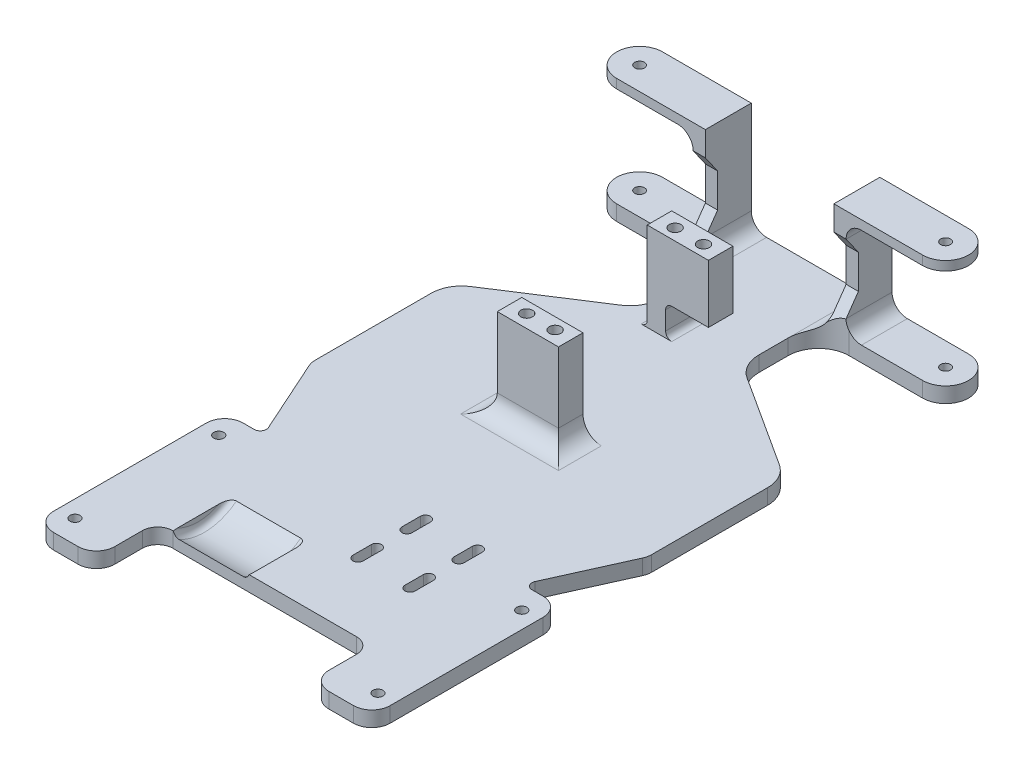
SolidWorks part; units mm, degrees
ref_plane "Front Plane" through (0, 0, 0) normal (0, 0, 1) x (1, 0, 0)
ref_plane "Top Plane" through (0, 0, 0) normal (0, 1, 0) x (1, 0, 0)
ref_plane "Right Plane" through (0, 0, 0) normal (1, 0, 0) x (0, 0, -1)
sketch "Sketch1" plane through (0, 0, 0) normal (0, 1, 0) x (1, 0, 0)
  line L1 (0, 0) -> (100, 0)
  line L2 (0, 0) -> (0, 15)
  line L3 (0, 15) -> (100, 15)
  line L4 (100, 0) -> (100, 15)
  circle A0 centre (100, 7.5) radius 7.5
  circle A1 centre (0, 7.5) radius 7.5
  circle A2 centre (0, 7.5) radius 1.6
  circle A3 centre (100, 7.5) radius 1.6
  dimension "D3" = 3.2
  dimension "D1" = 100
  dimension "D2" = 15
extrude "Boss-Extrude3" add sketch "Sketch1" along normal blind 5 contours A2 L2 A1 | A2 L2 A1 | A1 L1 A0 L3 | A3 L4 A0 | A3 L4 A0 region at (50, 0, -7.5) region at (-3.3025, 0, -7.5) region at (3.3025, 0, -7.5) region at (96.6975, 0, -7.5) region at (103.3025, 0, -7.5)
sketch "Sketch2" plane through (0, 5, 0) normal (0, 1, 0) x (1, 0, 0)
  line L0 (0, 15) -> (100, 15) construction
  line L1 (25, 15) -> (29, 15)
  line L2 (25, 15) -> (25, 0)
  line L3 (25, 0) -> (29, 0)
  line L4 (29, 15) -> (29, 0)
  line L5 (0, 0) -> (100, 0) construction
  line L6 (50, 0) -> (50, 15) construction
  line L7 (75, 0) -> (71, 0)
  line L8 (71, 15) -> (71, 0)
  line L9 (75, 15) -> (71, 15)
  line L10 (75, 15) -> (75, 0)
  circle A0 centre (0, 7.5) radius 1.6 construction
  dimension "D2" = 25
  dimension "D1" = 4
extrude "Boss-Extrude4" add sketch "Sketch2" along normal blind 32.5
sketch "Sketch3" plane through (0, 37.5, 0) normal (0, 1, 0) x (1, 0, 0)
  line L0 (75, 0) -> (75, 15) construction
  line L1 (75, 15) -> (71, 15) construction
  line L2 (71, 15) -> (71, 0) construction
  line L3 (71, 0) -> (75, 0) construction
  line L4 (25, 15) -> (25, 0) construction
  line L5 (25, 0) -> (29, 0) construction
  line L6 (29, 0) -> (29, 15) construction
  line L7 (29, 15) -> (25, 15) construction
  line L8 (25, 0) -> (25, 15) construction
  line L9 (25, 15) -> (0, 15) construction
  line L10 (0, 0) -> (25, 0) construction
  line L11 (100, 15) -> (75, 15) construction
  line L12 (75, 15) -> (75, 0) construction
  line L13 (75, 0) -> (100, 0) construction
  line L18 (75, 0) -> (75, 15)
  line L19 (75, 15) -> (71, 15)
  line L20 (71, 15) -> (71, 0)
  line L21 (71, 0) -> (75, 0)
  line L22 (25, 15) -> (25, 0)
  line L23 (25, 0) -> (29, 0)
  line L24 (29, 0) -> (29, 15)
  line L25 (29, 15) -> (25, 15)
  line L26 (25, 0) -> (25, 15)
  line L27 (25, 15) -> (0, 15)
  line L28 (0, 0) -> (25, 0)
  line L29 (100, 15) -> (75, 15)
  line L30 (75, 15) -> (75, 0)
  line L31 (75, 0) -> (100, 0)
  arc A0 (0, 15) -> (0, 0) centre (0, 7.5) ccw construction
  arc A1 (100, 0) -> (100, 15) centre (100, 7.5) ccw construction
  arc A2 (0, 15) -> (0, 0) centre (0, 7.5) ccw
  arc A3 (100, 0) -> (100, 15) centre (100, 7.5) ccw
  circle A4 centre (0, 7.5) radius 1.6
  circle A5 centre (100, 7.5) radius 1.6
  line M18 (25, 15) -> (25, 0)
  line M19 (25, 0) -> (29, 0)
  line M20 (29, 0) -> (29, 15)
  line M21 (29, 15) -> (25, 15)
  dimension "D1" = 3.2
extrude "Boss-Extrude6" add sketch "Sketch3" along normal blind 3 contours L31 A3 L29 L18 A5 | L20 L21 L18 L19 | L27 A2 L28 A4 M18 | M21 M18 M19 M20 region at (73, 37.5, -7.5) region at (90.3226, 37.5, -7.5) region at (27, 37.5, -7.5) region at (9.6774, 37.5, -7.5)
fillet "Fillet1" radius 5 6 edges at (75, 5, -7.5) (25, 5, -7.5) (75, 37.5, -7.5) (25, 37.5, -7.5) (71, 5, -7.5) (29, 5, -7.5)
sketch "Sketch4" plane through (29, 0, 0) normal (1, 0, 0) x (0, 0, -1)
  line L0 (0, 32.5) -> (0, 10) construction
  line L1 (0, 32.5) -> (4, 32.5) construction
  line L2 (0, 32.5) -> (0, 10)
  line L3 (0, 10) -> (4, 10)
  line L4 (4, 26.7874) -> (4, 15.7126)
  line L5 (0, 10) -> (15, 10) construction
  line L6 (15, 32.5) -> (0, 32.5) construction
  line L7 (0, 32.5) -> (4, 26.7874)
  line L8 (0, 10) -> (4, 15.7126)
  dimension "D1" = 4
  dimension "D2" = 55
  dimension "D3" = 4
  dimension "D4" = 4
extrude "Cut-Extrude1" cut sketch "Sketch4" against normal blind 10 and the other way through all contours L8 L4 L7 L2
sketch "Sketch5" plane through (0, 0, 0) normal (0, -1, 0) x (1, 0, 0)
  line L0 (0, -15) -> (100, -15) construction
  line L1 (40, -15) -> (60, -15)
  line L2 (40, -15) -> (40, 80)
  line L3 (40, 80) -> (60, 80)
  line L4 (60, -15) -> (60, 80)
  point P6 (50, -15)
  point P7 (50, -15)
  dimension "D1" = 20
  dimension "D2" = 95
extrude "Boss-Extrude7" add sketch "Sketch5" against normal blind 5
sketch "Sketch6" plane through (0, 5, 0) normal (0, 1, 0) x (1, 0, 0)
  line L0 (40, -80) -> (40, 0) construction
  line L1 (40, -30) -> (60, -30) construction
  line L2 (40, -30) -> (40, -71) construction
  line L3 (40, -71) -> (60, -71) construction
  line L4 (60, -30) -> (60, -71) construction
  line L5 (60, 0) -> (60, -80) construction
  line L6 (60, 0) -> (66, 0) construction
  line L7 (40, -22) -> (60, -22)
  line L8 (40, -71) -> (60, -71)
  line L9 (40, -71) -> (40, -79)
  line L10 (40, -79) -> (60, -79)
  line L11 (60, -71) -> (60, -79)
  line L12 (40, -22) -> (40, -30)
  line L13 (40, -30) -> (60, -30)
  line L14 (60, -22) -> (60, -30)
  dimension "D1" = 41
  dimension "D2" = 30
  dimension "D3" = 8
  dimension "D4" = 8
extrude "Boss-Extrude8" add sketch "Sketch6" along normal blind 29
sketch "Sketch7" plane through (0, 34, 0) normal (0, 1, 0) x (1, 0, 0)
  line L1 (50, -71) -> (50, -69.0543) construction
  line L2 (60, -71) -> (40, -71) construction
  line L3 (60, -50.5) -> (71.2332, -50.5) construction
  line L4 (60, -30) -> (60, -71) construction
  circle A0 centre (45.35, -74.75) radius 1.9
  circle A1 centre (54.65, -74.75) radius 1.9
  circle A2 centre (54.65, -26.25) radius 1.9
  circle A3 centre (45.35, -26.25) radius 1.9
  dimension "D1" = 48.5
  dimension "D3" = 3.8
  dimension "D2" = 9.3
extrude "Cut-Extrude2" cut sketch "Sketch7" against normal blind 6
sketch "Sketch8" plane through (60, 0, 0) normal (1, 0, 0) x (0, 0, -1)
  line L1 (-30, 5) -> (-22, 5)
  line L2 (-30, 5) -> (-30, 15)
  line L3 (-30, 15) -> (-22, 15)
  line L4 (-22, 5) -> (-22, 15)
  line L5 (-22, 34) -> (-22, 5) construction
  dimension "D1" = 10
extrude "Cut-Extrude3" cut sketch "Sketch8" against normal blind 14
fillet "Fillet3" radius 6 1 edges at (43, 5, 22)
fillet "Fillet4" radius 2 1 edges at (46, 5, 23)
fillet "Fillet5" radius 2 1 edges at (46, 15, 26)
sketch "Sketch9" plane through (0, 0, 0) normal (0, -1, 0) x (1, 0, 0)
  line L0 (34, 0) -> (34, 25)
  line L1 (34, 25) -> (-5, 50.2007)
  line L2 (-5, 50.2007) -> (-5, 185)
  line L3 (-5, 185) -> (105, 185)
  line L4 (66, 0) -> (66, 25)
  line L5 (50, -15) -> (50, 185) construction
  line L6 (34, -15) -> (66, -15) construction
  line L7 (66, 25) -> (105, 50.2007)
  line L8 (105, 50.2007) -> (105, 185)
  circle A0 centre (0.5, 177.5) radius 1.65
  circle A1 centre (0.5, 130.5) radius 1.65
  circle A2 centre (58, 139.5) radius 1.65
  circle A3 centre (58, 123.5) radius 1.65
  circle A4 centre (75, 139.5) radius 1.65
  circle A5 centre (75, 123.5) radius 1.65
  circle A6 centre (99.5, 130.5) radius 1.65
  circle A7 centre (99.5, 177.5) radius 1.65
  line M1 (100, 0) -> (60, 0)
  line M2 (60, 0) -> (60, 80)
  line M3 (60, 80) -> (40, 80)
  line M4 (40, 80) -> (40, 0)
  line M5 (40, 0) -> (0, 0)
  dimension "D5" = 3.3
  dimension "D4" = 5.5
  dimension "D8" = 16
  dimension "D9" = 3.3
  dimension "D1" = 200
  dimension "D2" = 25
  dimension "D3" = 55
  dimension "D6" = 47
  dimension "D7" = 7.5
  dimension "D10" = 17
  dimension "D11" = 8
  dimension "D12" = 9
extrude "Boss-Extrude9" add sketch "Sketch9" against normal blind 5 contours L5 L4 L7 L8 L3 A6 A5 A4 A3 A2 A7 M3 M2 M1 | L5 L3 L2 L1 L0 A0 A1 M3 M5 M4 region at (22.1581, 0, 111.2532) region at (77.8913, 0, 111.165)
fillet "Fillet6" radius 10 6 edges at (34, 2.5, 0) (66, 2.5, 0) (66, 2.5, 25) (34, 2.5, 25) (-5, 2.5, 50.2007) (105, 2.5, 50.2007)
fillet "Fillet7" radius 6 2 edges at (-5, 2.5, 185) (105, 2.5, 185)
fillet "Fillet8" radius 6 3 edges at (40, 5, 75) (60, 5, 75) (50, 5, 79)
sketch "Sketch10" plane through (0, 0, 0) normal (0, -1, 0) x (1, 0, 0)
  line L0 (1, 185) -> (99, 185) construction
  line L1 (15, 185) -> (85, 185)
  line L2 (15, 185) -> (15, 170)
  line L3 (20, 165) -> (80, 165)
  line L4 (85, 185) -> (85, 170)
  arc A0 (80, 165) -> (85, 170) centre (80, 170) ccw
  arc A1 (15, 170) -> (20, 165) centre (20, 170) ccw
  point P6 (50, 185)
  point P7 (50, 185)
  point P10 (85, 165)
  dimension "D3" = 5
  dimension "D1" = 70
  dimension "D2" = 20
extrude "Cut-Extrude4" cut sketch "Sketch10" against normal blind 5
fillet "Fillet9" radius 6 2 edges at (15, 2.5, 185) (85, 2.5, 185)
sketch "Sketch11" plane through (0, 0, 0) normal (0, -1, 0) x (1, 0, 0)
  line L0 (105, 123.0636) -> (92.2946, 123.0636)
  line L1 (105, 55.645) -> (105, 179) construction
  line L2 (92.2946, 123.0636) -> (105, 94.8251)
  line L3 (105, 94.8251) -> (105, 123.0636)
  line L4 (-5, 123.0636) -> (7.7054, 123.0636)
  line L5 (-5, 55.645) -> (-5, 179) construction
  line L6 (7.7054, 123.0636) -> (-5, 94.8251)
  line L7 (-5, 94.8251) -> (-5, 123.0636)
extrude "Cut-Extrude5" cut sketch "Sketch11" against normal blind 5
fillet "Fillet10" radius 6 4 edges at (105, 2.5, 94.8251) (-5, 2.5, 94.8251) (105, 2.5, 123.0636) (-5, 2.5, 123.0636)
fillet "Fillet11" radius 2 2 edges at (7.7054, 2.5, 123.0636) (92.2946, 2.5, 123.0636)
sketch "Sketch12" plane through (-5, 0, 0) normal (-1, 0, 0) x (0, 0, 1)
  line L0 (129.0636, 5) -> (179, 5) construction
  line L2 (146.2403, 5) -> (167.2403, 5)
  arc A0 (146.2403, 5) -> (167.2403, 5) centre (156.7403, 18.3697) ccw
  dimension "D1" = 17
  dimension "D2" = 21
extrude "Cut-Extrude6" cut sketch "Sketch12" against normal blind 25 from offset 25 offset against normal yes
fillet "Fillet12" radius 2 2 edges at (20, 1.423, 155.3953) (45, 1.423, 155.3953)
fillet "Fillet13" radius 2 1 edges at (40, 5, 23)
sketch "Sketch13" plane through (0, 0, 0) normal (0, -1, 0) x (1, 0, 0)
  line L0 (58, 142.5) -> (58, 136.5) construction
  line L1 (59.65, 142.5) -> (59.65, 136.5)
  line L2 (56.35, 142.5) -> (56.35, 136.5)
  line L3 (73.35, 142.5) -> (73.35, 136.5)
  line L4 (76.65, 142.5) -> (76.65, 136.5)
  line L5 (75, 142.5) -> (75, 136.5) construction
  line L6 (73.35, 126.5) -> (73.35, 120.5)
  line L7 (76.65, 126.5) -> (76.65, 120.5)
  line L8 (75, 126.5) -> (75, 120.5) construction
  line L9 (56.35, 126.5) -> (56.35, 120.5)
  line L10 (59.65, 126.5) -> (59.65, 120.5)
  line L11 (58, 126.5) -> (58, 120.5) construction
  arc A0 (59.65, 142.5) -> (56.35, 142.5) centre (58, 142.5) ccw
  arc A1 (56.35, 136.5) -> (59.65, 136.5) centre (58, 136.5) ccw
  circle A2 centre (58, 139.5) radius 1.65 construction
  arc A3 (76.65, 142.5) -> (73.35, 142.5) centre (75, 142.5) ccw
  arc A4 (73.35, 136.5) -> (76.65, 136.5) centre (75, 136.5) ccw
  arc A5 (76.65, 126.5) -> (73.35, 126.5) centre (75, 126.5) ccw
  arc A6 (73.35, 120.5) -> (76.65, 120.5) centre (75, 120.5) ccw
  arc A7 (59.65, 126.5) -> (56.35, 126.5) centre (58, 126.5) ccw
  arc A8 (56.35, 120.5) -> (59.65, 120.5) centre (58, 120.5) ccw
  point P2 (58, 139.5)
  point P14 (75, 139.5)
  point P21 (75, 123.5)
  point P28 (58, 123.5)
  dimension "D1" = 6
  dimension "D4" = 16
  dimension "D2" = 2
  dimension "D3" = 2
extrude "Cut-Extrude7" cut sketch "Sketch13" against normal blind 15
